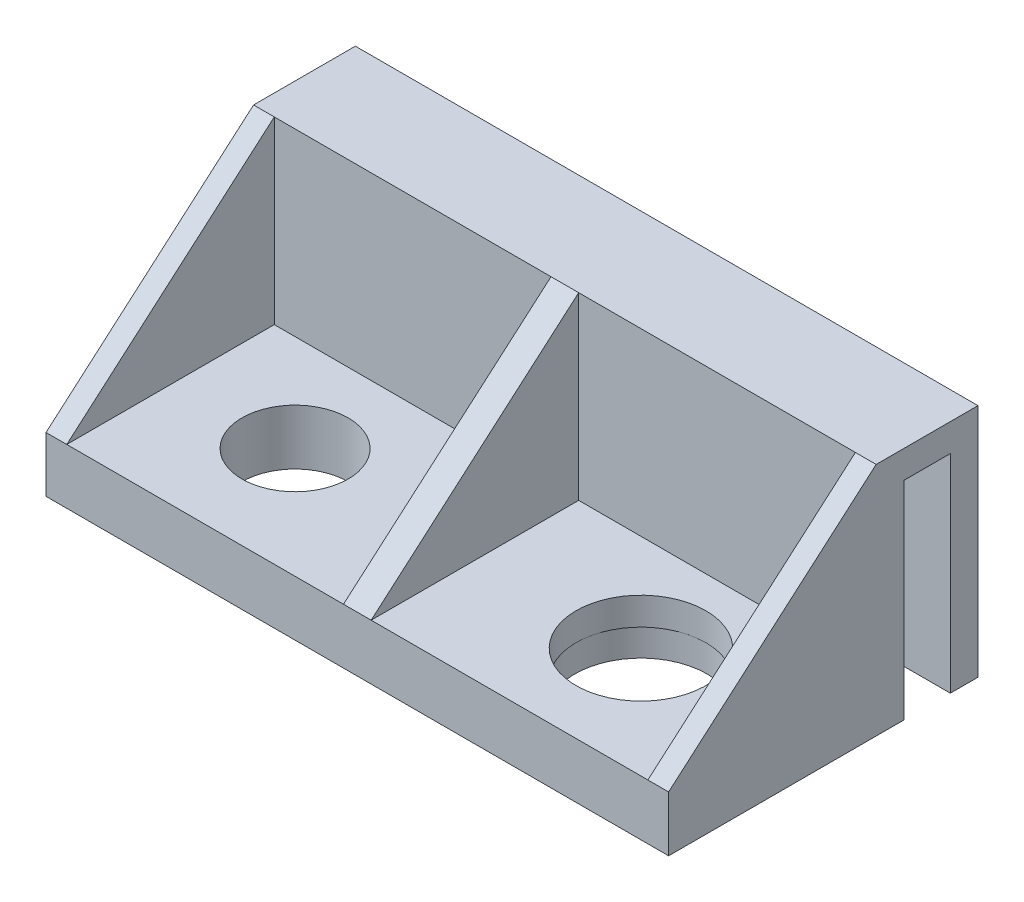
SolidWorks part; units mm, degrees
material "ABS PC"
ref_plane "Front Plane" through (0, 0, 0) normal (0, 0, 1) x (1, 0, 0)
ref_plane "Top Plane" through (0, 0, 0) normal (0, 1, 0) x (1, 0, 0)
ref_plane "Right Plane" through (0, 0, 0) normal (1, 0, 0) x (0, 0, -1)
sketch "Sketch1" plane through (0, 0, 0) normal (1, 0, 0) x (0, 0, -1)
  line L0 (0, -13) -> (0, 17)
  line L1 (0, 17) -> (-7.36, 17)
  line L2 (-7.36, 17) -> (-7.36, 4)
  line L3 (-7.36, 4) -> (-22.36, 4)
  line L4 (-22.36, 4) -> (-22.36, 0)
  line L5 (-22.36, 0) -> (-7.36, 0)
  line L6 (-7.36, 0) -> (-7.36, -13)
  line L7 (-7.36, -13) -> (0, -13)
  dimension "D1" = 30
  dimension "D2" = 4
  dimension "D3" = 7.36
  dimension "D4" = 15
extrude "Boss-Extrude1" add sketch "Sketch1" along normal mid plane 45
sketch "Sketch2" plane through (22.5, 0, 0) normal (1, 0, 0) x (0, 0, -1)
  line L0 (-7.36, -13) -> (0, -13) construction
  line L1 (-2, -13) -> (-5.36, -13)
  line L2 (-2, -13) -> (-2, 15)
  line L3 (-2, 15) -> (-5.36, 15)
  line L4 (-5.36, -13) -> (-5.36, 15)
  line L5 (0, 17) -> (-7.36, 17) construction
  point P6 (-3.68, -13)
  dimension "D1" = 3.36
  dimension "D2" = 2
extrude "Cut-Extrude1" cut sketch "Sketch2" against normal through all
sketch "Sketch3" plane through (22.5, 0, 0) normal (1, 0, 0) x (0, 0, -1)
  line L1 (-7.36, 0) -> (0, 0)
  line L2 (-7.36, 0) -> (-7.36, -13)
  line L3 (-7.36, -13) -> (0, -13)
  line L4 (0, 0) -> (0, -13)
extrude "Cut-Extrude2" cut sketch "Sketch3" against normal through all
sketch "Sketch4" plane through (0, 0, 0) normal (0, -1, 0) x (-1, 0, 0)
  line L0 (-22.5, -22.36) -> (-22.5, -5.36) construction
  line L1 (-22.5, -22.36) -> (22.5, -22.36) construction
  line L2 (22.5, -22.36) -> (22.5, -5.36) construction
  circle A0 centre (-12.5, -14.36) radius 4.69
  circle A1 centre (12.5, -14.36) radius 3.835
  dimension "D1" = 9.38
  dimension "D5" = 7.67
  dimension "D2" = 10
  dimension "D3" = 8
  dimension "D4" = 10
extrude "Cut-Extrude3" cut sketch "Sketch4" against normal blind 10
sketch "Sketch6" plane through (0, 0, 0) normal (0, -1, 0) x (-1, 0, 0)
  circle A0 centre (-12.5, -14.36) radius 4.775
  dimension "D1" = 9.55
extrude "Cut-Extrude5" cut sketch "Sketch6" against normal blind 2
sketch "Sketch7" plane through (-22.5, 0, 0) normal (-1, 0, 0) x (0, 0, 1)
  line L0 (22.36, 4) -> (7.36, 17)
rib "Rib2" sketch "Sketch7" sketch "Sketch7" thickness 1.5 extrusion direction parallel to sketch draft on no parameters "D1"=1.5
sketch "Sketch8" plane through (22.5, 0, 0) normal (1, 0, 0) x (0, 0, -1)
  line L0 (-22.36, 4) -> (-7.36, 17)
rib "Rib3" sketch "Sketch8" sketch "Sketch8" thickness 1.5 extrusion direction parallel to sketch draft on no parameters "D1"=1.5
sketch "Sketch9" plane through (0, 0, 0) normal (1, 0, 0) x (0, 0, -1)
  line L0 (-22.36, 4) -> (-7.36, 17)
rib "Rib4" sketch "Sketch9" sketch "Sketch9" thickness 2 extrusion direction parallel to sketch draft on no parameters "D1"=2
